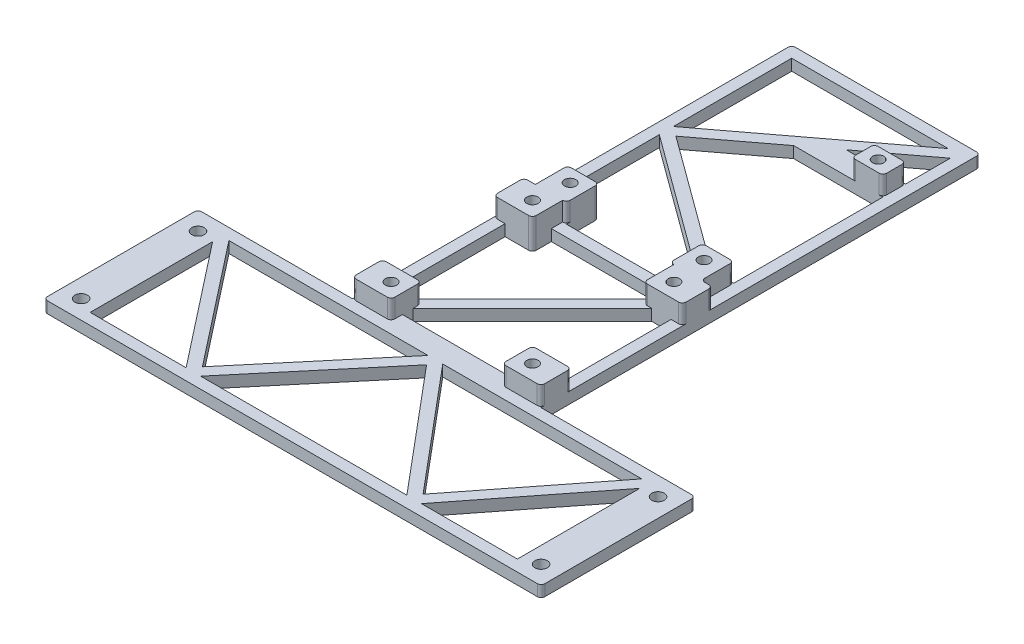
SolidWorks part; units mm, degrees
ref_plane "Front Plane" through (0, 0, 0) normal (0, 0, 1) x (1, 0, 0)
ref_plane "Top Plane" through (0, 0, 0) normal (0, 1, 0) x (1, 0, 0)
ref_plane "Right Plane" through (0, 0, 0) normal (1, 0, 0) x (0, 0, -1)
sketch "Sketch1" plane through (0, 0, 0) normal (0, 1, 0) x (1, 0, 0)
  line L0 (0, -55) -> (0, 55) construction
  line L1 (-65.95, -40.9) -> (65.95, -40.9)
  line L2 (-65.95, -40.9) -> (-65.95, 0)
  line L3 (-65.95, 0) -> (65.95, 0)
  line L4 (65.95, -40.9) -> (65.95, 0)
  line L5 (-56.65, 0) -> (-56.65, -40.9)
  line L6 (56.65, 0) -> (56.65, -40.9)
  line L7 (-56.65, -3) -> (56.65, -3)
  line L8 (-56.65, -37.9) -> (56.65, -37.9)
  line L9 (-56.65, -3) -> (-29.3, -37.9) construction
  line L10 (-29.3, -37.9) -> (0, -3) construction
  line L11 (-54.7443, -3) -> (-29.2599, -35.5194)
  line L12 (-56.65, -5.4318) -> (-31.2057, -37.9)
  line L13 (-29.2599, -35.5194) -> (-1.9585, -3)
  line L14 (-27.3415, -37.9) -> (0, -5.3329)
  line L15 (0, -3) -> (0, -37.9) construction
  line L16 (56.65, -5.4318) -> (31.2057, -37.9)
  line L17 (56.65, -3) -> (29.3, -37.9) construction
  line L18 (54.7443, -3) -> (29.2599, -35.5194)
  line L19 (27.3415, -37.9) -> (0, -5.3329)
  line L20 (29.3, -37.9) -> (0, -3) construction
  line L21 (29.2599, -35.5194) -> (1.9585, -3)
  line L22 (0, 115) -> (0, 0) construction
  line L23 (-25, 0) -> (25, 0)
  line L24 (-25, 0) -> (-25, 115)
  line L25 (-25, 115) -> (25, 115)
  line L26 (25, 0) -> (25, 115)
  line L27 (-25, 45.5) -> (25, 45.5)
  line L28 (13.75, 54.1) -> (-22, 80.25) construction
  line L29 (-22, 80.25) -> (22, 113.5) construction
  line L30 (13.75, 52.2415) -> (-22, 78.3915)
  line L31 (25, 80.25) -> (-25, 80.25) construction
  line L32 (-19.4593, 80.25) -> (16.2907, 54.1)
  line L33 (-19.4593, 80.25) -> (22, 111.58)
  line L34 (-22, 82.1301) -> (19.512, 113.5)
  line L35 (-25, 8) -> (-14.75, 8)
  line L36 (-25, 116.5) -> (25, 116.5)
  line L37 (-25, 116.5) -> (-25, 113.5)
  line L38 (-25, 113.5) -> (25, 113.5)
  line L39 (25, 116.5) -> (25, 113.5)
  line L40 (-22, 45.5) -> (-25, 45.5)
  line L41 (-22, 45.5) -> (-22, 115)
  line L42 (-22, 115) -> (-25, 115)
  line L43 (-25, 45.5) -> (-25, 115)
  line L44 (25, 45.5) -> (22, 45.5)
  line L45 (25, 45.5) -> (25, 115)
  line L46 (25, 115) -> (22, 115)
  line L47 (22, 45.5) -> (22, 115)
  line L48 (25, 45.5) -> (14.75, 45.5)
  line L49 (25, 45.5) -> (25, 37.5)
  line L50 (25, 37.5) -> (14.75, 37.5)
  line L51 (14.75, 45.5) -> (14.75, 37.5)
  line L52 (25, 0) -> (14.75, 0)
  line L53 (25, 0) -> (25, 8)
  line L54 (25, 8) -> (14.75, 8)
  line L55 (14.75, 0) -> (14.75, 8)
  line L56 (25, 37.5) -> (22, 37.5)
  line L57 (25, 37.5) -> (25, 8)
  line L58 (25, 8) -> (22, 8)
  line L59 (22, 37.5) -> (22, 8)
  line L60 (-14.75, 0) -> (-14.75, 8)
  line L61 (-25, 0) -> (-14.75, 0)
  line L62 (-25, 0) -> (-25, 8)
  line L63 (-25, 8) -> (-22, 8)
  line L64 (-22, 37.5) -> (-22, 8)
  line L65 (-25, 37.5) -> (-22, 37.5)
  line L66 (-25, 37.5) -> (-25, 8)
  line L67 (-25, 37.5) -> (-14.75, 37.5)
  line L68 (-14.75, 45.5) -> (-14.75, 37.5)
  line L69 (-25, 45.5) -> (-14.75, 45.5)
  line L70 (-25, 45.5) -> (-25, 37.5)
  line L71 (-14.75, 8) -> (14.75, 37.5) construction
  line L72 (-14.75, 45.5) -> (14.75, 45.5)
  line L73 (-14.75, 45.5) -> (-14.75, 42.5)
  line L74 (-14.75, 42.5) -> (14.75, 42.5)
  line L75 (14.75, 45.5) -> (14.75, 42.5)
  line L76 (-14.75, 0) -> (14.75, 0)
  line L77 (-14.75, 0) -> (-14.75, 3)
  line L78 (-14.75, 3) -> (14.75, 3)
  line L79 (14.75, 0) -> (14.75, 3)
  line L80 (-16.8713, 8) -> (14.75, 39.6213)
  line L81 (16.8713, 37.5) -> (-14.75, 5.8787)
  line L82 (-25, 54.1) -> (-13.75, 54.1)
  line L83 (25, 45.5) -> (13.75, 45.5)
  line L84 (25, 45.5) -> (25, 54.1)
  line L85 (25, 54.1) -> (13.75, 54.1)
  line L86 (13.75, 45.5) -> (13.75, 54.1)
  line L87 (-13.75, 45.5) -> (-13.75, 54.1)
  line L88 (-25, 45.5) -> (-13.75, 45.5)
  line L89 (-25, 45.5) -> (-25, 54.1)
  line L90 (22, 99.7) -> (6.2791, 99.7)
  line L91 (-1.6608, 93.7) -> (22, 93.7)
  line L92 (13.75, 99.7) -> (13.75, 93.7)
  circle A0 centre (61, -4.95) radius 1.65
  circle A1 centre (61, -35.95) radius 1.65
  circle A2 centre (-61, -35.95) radius 1.65
  circle A3 centre (-61, -4.95) radius 1.65
  circle A4 centre (-18.75, 4) radius 1.5
  circle A5 centre (-18.75, 41.5) radius 1.5
  circle A6 centre (18.75, 4) radius 1.5
  circle A7 centre (18.75, 41.5) radius 1.5
  circle A8 centre (17.75, 50.5) radius 1.5
  circle A9 centre (-17.75, 50.5) radius 1.5
  circle A10 centre (17.75, 96.7) radius 1.5
  point P5 (0, 0)
  point P79 (14.75, 4)
  dimension "D3" = 3.3
  dimension "D5" = 4.95
  dimension "D6" = 3.3
  dimension "D7" = 4.95
  dimension "D8" = 4.95
  dimension "D20" = 3
  dimension "D22" = 4
  dimension "D23" = 3
  dimension "D42" = 3
  dimension "D47" = 3
  dimension "D1" = 131.9
  dimension "D2" = 40.9
  dimension "D4" = 4.95
  dimension "D9" = 9.3
  dimension "D10" = 9.3
  dimension "D11" = 3
  dimension "D12" = 3
  dimension "D13" = 27.35
  dimension "D14" = 1.5
  dimension "D15" = 1.5
  dimension "D16" = 1.5
  dimension "D17" = 1.5
  dimension "D18" = 50
  dimension "D19" = 115
  dimension "D21" = 18.75
  dimension "D24" = 37.5
  dimension "D25" = 4
  dimension "D26" = 34.75
  dimension "D27" = 1.5
  dimension "D28" = 1.5
  dimension "D29" = 1.5
  dimension "D30" = 3
  dimension "D31" = 3
  dimension "D32" = 3
  dimension "D33" = 4
  dimension "D34" = 4
  dimension "D35" = 4
  dimension "D36" = 4
  dimension "D37" = 3
  dimension "D38" = 3
  dimension "D39" = 3
  dimension "D40" = 1.5
  dimension "D41" = 1.5
  dimension "D43" = 17.75
  dimension "D44" = 5
  dimension "D45" = 3.6
  dimension "D46" = 4
  dimension "D48" = 46.2
  dimension "D49" = 7.25
  dimension "D50" = 1.5
  dimension "D51" = 3
  dimension "D52" = 3
  dimension "D53" = 4
extrude "Boss-Extrude1" add sketch "Sketch1" along normal blind 3 contours L8 L5 L1 L6 | L5 L3 L2 L1 A2 A3 | L18 L21 L7 L13 L11 L5 L12 L8 L14 L19 L16 L6 | L3 L6 L1 L4 A1 A0 | L5 L7 L6 L3 L23 | L78 L60 L23 L55 | L55 L23 L26 L54 A6 | L3 L60 L35 L24 A4 | L50 L59 L54 L26 | L81 L50 L51 L80 L35 L60 | L65 L24 L35 L64 | L27 L51 L50 L26 A7 | L68 L74 L51 L72 L27 | L68 L27 L24 L65 L67 A5 | L27 L87 L82 L41 A9 | L82 L24 L27 L41 | L86 L72 L27 L47 L85 A8 | L26 L85 L47 L27 | L30 L86 L85 L32 L33 L47 L38 L34 L41 | L85 L45 L38 L47 | L43 L82 L41 L38 | L92 L90 L33 L91 | L90 L92 L91 L47 A10 | L38 L47 L25 L41 | L39 L36 L37 L25 | L47 L38 L26 L25 | L38 L41 L25 L24 region at (-61.3141, 0, 20.45) region at (0, 0, 39.4) region at (61.3141, 0, 20.45) region at (0, 0, 1.5) region at (-55.4645, 0, 4.2159) region at (-24.87, 0, -4) region at (0, 0, -1.5) region at (-23.5, 0, -22.75) region at (14.88, 0, -1.5) region at (-24.87, 0, -41.5) region at (0, 0, -22.75) region at (-23.5, 0, -49.8) region at (23.5, 0, -22.75) region at (15.8107, 0, -37.63) region at (-23.5, 0, -83.8) region at (-21.8808, 0, -49.8) region at (-23.5, 0, -114.25) region at (0, 0, -44) region at (23.5, 0, -49.8) region at (0, 0, -115.75) region at (0, 0, -114.25) region at (-21.2458, 0, -80.2608) region at (14.25, 0, -45.6192) region at (23.5, 0, -83.8) region at (23.5, 0, -114.25) region at (17.875, 0, -93.802) region at (7.8, 0, -96.353)
extrude "Boss-Extrude2" add sketch "Sketch1<5>" along normal blind 5 from surface contours L55 L23 L26 L54 A6 | L3 L60 L35 L24 A4 | L27 L51 L50 L26 A7 | L68 L27 L24 L65 L67 A5 | L86 L72 L27 L47 L85 A8 | L27 L87 L82 L41 A9 | L90 L92 L91 L47 A10 region at (-24.87, 0, -4) region at (14.88, 0, -1.5) region at (-24.87, 0, -41.5) region at (15.8107, 0, -37.63) region at (-21.8808, 0, -49.8) region at (14.25, 0, -45.6192) region at (17.875, 0, -93.802) starting at face at (0, 3, -18.9)
sketch "Sketch1<5>" plane through (0, 0, 0) normal (0, 1, 0) x (1, 0, 0) same geometry as "Sketch1"
fillet "Fillet1" radius 1 31 edges at (25, 1.5, -116.5) (22, 5.5, -99.7) (22, 5.5, -93.7) (13.75, 5.5, -99.7) (13.75, 5.5, -93.7) (-25, 1.5, -116.5) (-65.95, 1.5, 0) (-65.95, 1.5, 40.9) (-25, 5.5, -8) (-25, 5.5, 0) (-14.75, 5.5, 0) (-14.75, 5.5, -8) (14.75, 5.5, 0) (14.75, 4, -8) (25, 5.5, -8) (25, 5.5, 0) (65.95, 1.5, 40.9) (65.95, 1.5, 0) (13.75, 5.5, -45.5) (13.75, 5.5, -54.1) (22, 5.5, -54.1) (22, 5.5, -45.5) (25, 5.5, -45.5) (25, 5.5, -37.5) (14.75, 5.5, -37.5) (-22, 5.5, -54.1) (-25, 5.5, -45.5) (-25, 5.5, -37.5) (-14.75, 4, -37.5) (-13.75, 5.5, -45.5) (-13.75, 4, -54.1)
